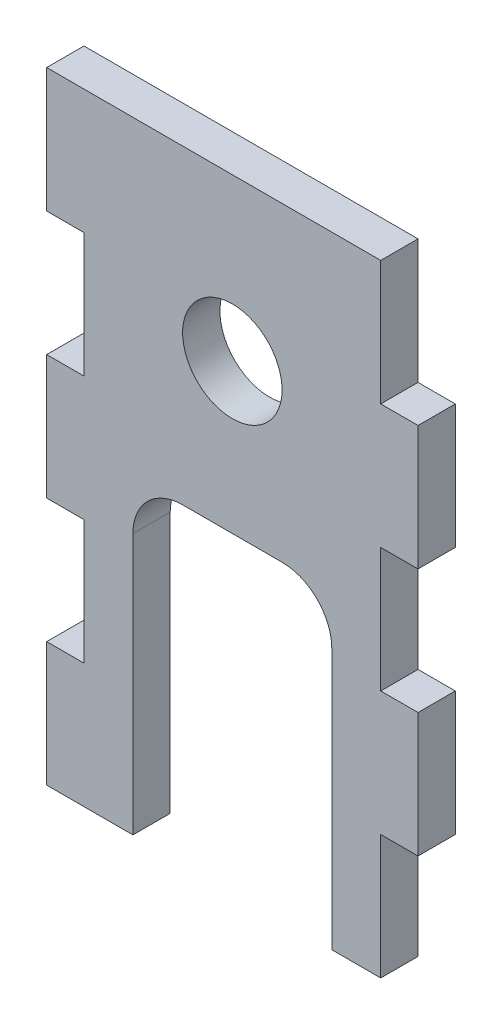
SolidWorks part; units mm, degrees
ref_plane "Front Plane" through (0, 0, 0) normal (0, 0, 1) x (1, 0, 0)
ref_plane "Top Plane" through (0, 0, 0) normal (0, 1, 0) x (1, 0, 0)
ref_plane "Right Plane" through (0, 0, 0) normal (1, 0, 0) x (0, 0, -1)
sketch "Sketch1" plane through (0, 0, 0) normal (0, 0, 1) x (1, 0, 0)
  line L1 (-11.938, -25) -> (11.938, -25)
  line L2 (-11.938, -25) -> (-11.938, 25)
  line L3 (-11.938, 25) -> (11.938, 25)
  line L4 (11.938, -25) -> (11.938, 25)
  line L5 (-11.938, -25) -> (11.938, 25) construction
  line L6 (-11.938, 25) -> (11.938, -25) construction
  point P0 (0, 0)
  dimension "D1" = 50
  dimension "D2" = 23.876
extrude "Boss-Extrude1" add sketch "Sketch1" along normal blind 3 contours L2 L3 L4 L1
sketch "Sketch2" plane through (0, 0, 3) normal (0, 0, 1) x (1, 0, 0)
  line L0 (-11.938, -25) -> (11.938, -25) construction
  line L1 (-8, 0) -> (8, 0)
  line L2 (-8, 0) -> (-8, -25)
  line L3 (-8, -25) -> (8, -25)
  line L4 (8, 0) -> (8, -25)
  line L5 (-8, 0) -> (8, -25) construction
  line L6 (-8, -25) -> (8, 0) construction
  circle A0 centre (0, 12) radius 4
  point P2 (0, -12.5)
  dimension "D1" = 8
  dimension "D2" = 12
  dimension "D3" = 16
extrude "Cut-Extrude1" cut sketch "Sketch2" against normal through all
fillet "Fillet1" radius 4 2 edges at (8, 0, 1.5) (-8, 0, 1.5)
sketch "Sketch3" plane through (0, 0, 0) normal (0, 0, -1) x (-1, 0, 0)
  line L0 (11.938, 5) -> (11.938, -5)
  line L1 (11.938, 25) -> (14.938, 25)
  line L2 (11.938, 25) -> (11.938, 15)
  line L3 (11.938, 15) -> (14.938, 15)
  line L4 (14.938, 25) -> (14.938, 15)
  line L5 (11.938, 5) -> (14.938, 5)
  line L6 (14.938, 5) -> (14.938, -5)
  line L7 (11.938, -5) -> (14.938, -5)
  line L8 (11.938, -15) -> (11.938, -25)
  line L9 (11.938, -15) -> (14.938, -15)
  line L10 (14.938, -15) -> (14.938, -25)
  line L11 (11.938, -25) -> (14.938, -25)
  line L12 (11.938, -25) -> (11.938, 25) construction
  line L13 (-11.938, -25) -> (-11.938, 25) construction
  line L14 (-11.938, 15) -> (-14.938, 15)
  line L15 (-11.938, 15) -> (-11.938, 5)
  line L16 (-11.938, 5) -> (-14.938, 5)
  line L17 (-14.938, 15) -> (-14.938, 5)
  line L18 (11.938, -25) -> (8, -25) construction
  line L19 (-11.938, -5) -> (-14.938, -5)
  line L20 (-11.938, -5) -> (-11.938, -15)
  line L21 (-11.938, -15) -> (-14.938, -15)
  line L22 (-14.938, -5) -> (-14.938, -15)
  dimension "D1" = 3
  dimension "D2" = 10
  dimension "D3" = 3
extrude "Boss-Extrude2" add sketch "Sketch3" against normal up to surface (3 mm away) up to face at (0, -5.6343, 3)
equation "\"pulley_pitch_diam\"= 12.73mm"
equation "\"pulley_total_width\"= 16mm"
equation "\"belt_width\"= 6mm"
equation "\"material_thickness\"= 3mm"
equation "\"D1@Boss-Extrude1\"=\"material_thickness\""
equation "\"shaft_diam\"= 8mm"
equation "\"D1@Sketch2\"=\"shaft_diam\""
equation "\"pulley_total_diam\"= 16mm"
equation "\"D2@Sketch2\"=\"pulley_total_diam\" * 0.75"
equation "\"D3@Sketch2\"=\"pulley_total_width\""
equation "\"D1@Sketch1\"=50mm"
equation "\"D1@Sketch3\"=\"material_thickness\""
